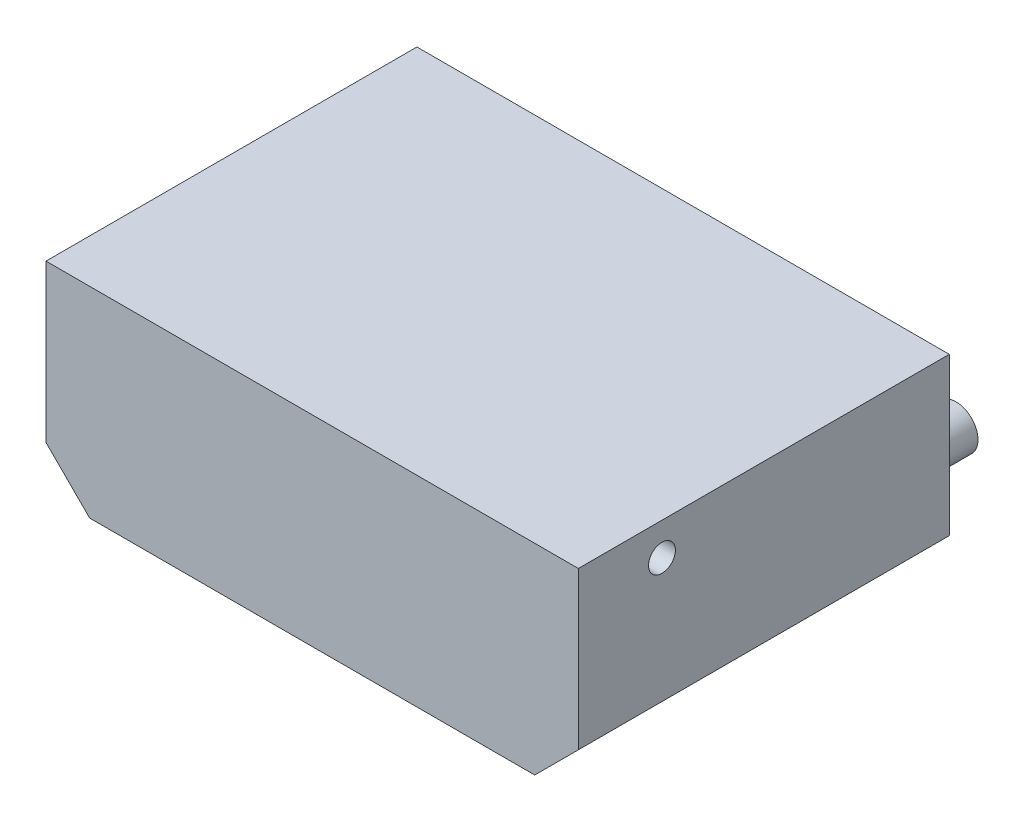
SolidWorks part; units mm, degrees
ref_plane "Front Plane" through (0, 0, 0) normal (0, 0, 1) x (1, 0, 0)
ref_plane "Top Plane" through (0, 0, 0) normal (0, 1, 0) x (1, 0, 0)
ref_plane "Right Plane" through (0, 0, 0) normal (1, 0, 0) x (0, 0, -1)
sketch "Sketch1" plane through (0, 0, 0) normal (0, 0, 1) x (1, 0, 0)
  line L0 (-102, -46) -> (-122, -26)
  line L1 (102, -46) -> (-102, -46)
  line L2 (122, -26) -> (122, 46)
  line L3 (122, 46) -> (-122, 46)
  line L4 (-122, -26) -> (-122, 46)
  line L5 (122, -46) -> (-122, 46) construction
  line L6 (122, 46) -> (-122, -46) construction
  line L7 (122, -26) -> (102, -46)
  point P0 (0, 0)
  dimension "D1" = 244
  dimension "D2" = 92
extrude "Boss-Extrude1" add sketch "Sketch1" along normal blind 170
sketch "Sketch2" plane through (0, -46, 0) normal (0, -1, 0) x (1, 0, 0)
  line L0 (-102, 85) -> (102, 85) construction
  line L1 (-102, 170) -> (-102, 0) construction
  line L2 (102, 170) -> (102, 0) construction
  line L3 (-102, 170) -> (102, 170) construction
  line L4 (87, 15) -> (-87, 15)
  line L5 (87, 15) -> (87, 155)
  line L6 (87, 155) -> (-87, 155)
  line L7 (-87, 15) -> (-87, 155)
  line L8 (87, 15) -> (-87, 155) construction
  line L9 (87, 155) -> (-87, 15) construction
  point P6 (0, 85)
  dimension "D1" = 15
  dimension "D2" = 15
extrude "Cut-Extrude1" cut sketch "Sketch2" against normal blind 0.1
sketch "Sketch3" plane through (0, 0, 0) normal (0, 0, -1) x (-1, 0, 0)
  circle A0 centre (-76.4755, 0) radius 10
  circle A1 centre (-106.4755, 0) radius 10
  point P4 (0, 0)
  dimension "D1" = 20
  dimension "D2" = 20
  dimension "D3" = 30
extrude "Boss-Extrude2" add sketch "Sketch3" along normal blind 18.7
sketch "Sketch4" plane through (0, -45.9, 0) normal (0, -1, 0) x (1, 0, 0)
  text T0 "<b>VIDEOJET</b>" font "Times New Roman" height in points 72
extrude "Cut-Extrude2" cut sketch "Sketch4" against normal blind 0.1
sketch "Sketch5" plane through (122, 0, 0) normal (1, 0, 0) x (0, 0, -1)
  circle A0 centre (-131.6684, 31.0703) radius 6.1604
extrude "Cut-Extrude3" cut sketch "Sketch5" against normal up to next
